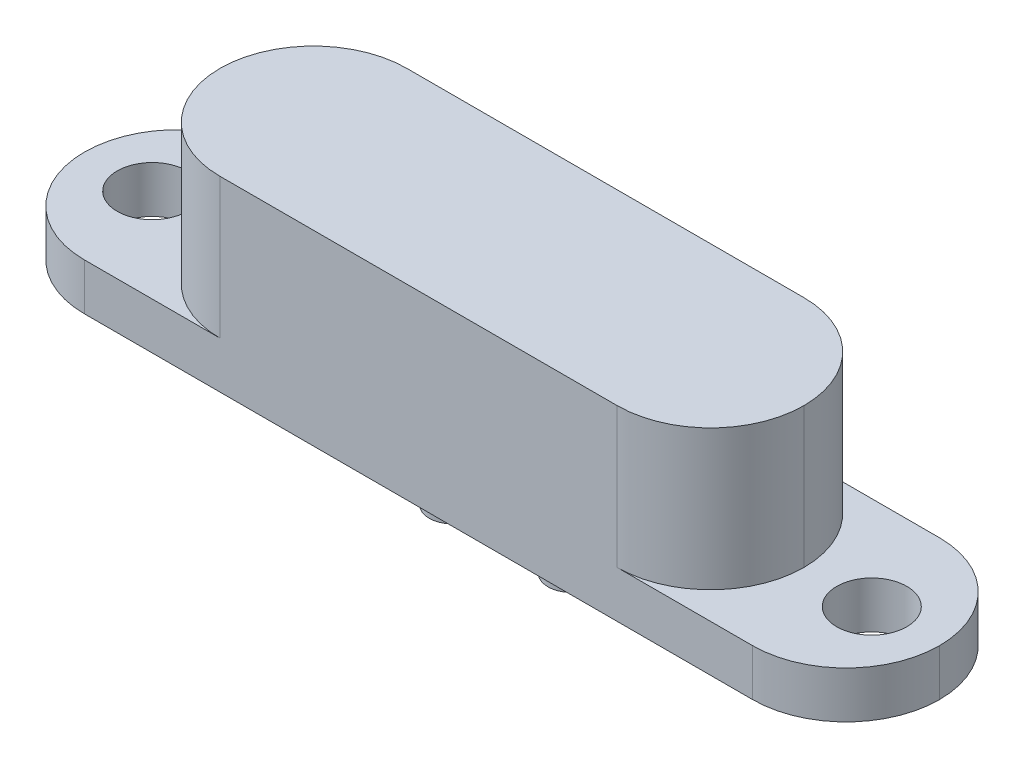
SolidWorks part; units mm, degrees
ref_plane "前视基准面" through (0, 0, 0) normal (0, 0, 1) x (1, 0, 0)
ref_plane "上视基准面" through (0, 0, 0) normal (0, 1, 0) x (1, 0, 0)
ref_plane "右视基准面" through (0, 0, 0) normal (1, 0, 0) x (0, 0, -1)
other "Configuration Table"
sketch "草图1" plane through (0, 0, 0) normal (0, 1, 0) x (1, 0, 0)
  line L1 (-9.15, -2) -> (9.15, -2)
  line L2 (-9.15, -2) -> (-9.15, 2)
  line L3 (-9.15, 2) -> (9.15, 2)
  line L4 (9.15, -2) -> (9.15, 2)
  line L5 (-9.15, -2) -> (9.15, 2) construction
  line L6 (-9.15, 2) -> (9.15, -2) construction
  line L7 (-6.25, -2) -> (6.25, -2)
  line L8 (-6.25, -2) -> (-6.25, 2)
  line L9 (-6.25, 2) -> (6.25, 2)
  line L10 (6.25, -2) -> (6.25, 2)
  line L11 (-6.25, -2) -> (6.25, 2) construction
  line L12 (-6.25, 2) -> (6.25, -2) construction
  point P0 (0, 0)
  point P7 (0, 0)
  dimension "D1" = 4
  dimension "D2" = 18.3
  dimension "D3" = 12.5
extrude "凸台-拉伸1" add sketch "草图1" along normal blind 4 contours L8 L9 L10 L7
fillet "圆角1" radius 2 4 edges at (6.25, 2, -2) (6.25, 2, 2) (-6.25, 2, 2) (-6.25, 2, -2)
extrude "凸台-拉伸2" add sketch "草图1<3>" along normal blind 1 contours L2 L3 L4 L1
sketch "草图1<3>" plane through (0, 0, 0) normal (0, 1, 0) x (1, 0, 0) same geometry as "草图1"
fillet "圆角2" radius 2 4 edges at (9.15, 0.5, 2) (9.15, 0.5, -2) (-9.15, 0.5, 2) (-9.15, 0.5, -2)
sketch "草图2" plane through (0, 1, 0) normal (0, 1, 0) x (1, 0, 0)
  line L0 (-9.15, 0) -> (-6.25, 0) construction
  line L1 (6.25, 0) -> (9.15, 0) construction
  arc A0 (-6.25, 0) -> (-4.25, -2) centre (-4.25, 0) ccw construction
  circle A1 centre (-7.7, 0) radius 0.75
  arc A2 (4.25, -2) -> (6.25, 0) centre (4.25, 0) ccw construction
  circle A3 centre (7.7, 0) radius 0.75
  dimension "D1" = 1.5
extrude "切除-拉伸1" cut sketch "草图2" against normal through all
sketch "草图3" plane through (0, 0, 0) normal (0, -1, 0) x (1, 0, 0)
  line L0 (-1.27, 0) -> (0, 0) construction
  line L7 (0, 0) -> (1.27, 0) construction
  circle A0 centre (-1.27, 0) radius 0.5
  circle A1 centre (1.27, 0) radius 0.5
  point P0 (0, 0)
  dimension "D2" = 1
  dimension "D1" = 2.54
extrude "凸台-拉伸3" add sketch "草图3" along normal blind 5.6 from surface starting at face at (0, 4, 0)
sketch "草图4" plane through (0, 0, 0) normal (0, -1, 0) x (1, 0, 0)
  circle A0 centre (0, 0) radius 0.5
  point P2 (0.4195, -0.5539)
  dimension "D1" = 1
extrude "切除-拉伸2" cut sketch "草图4" against normal blind 0.1
